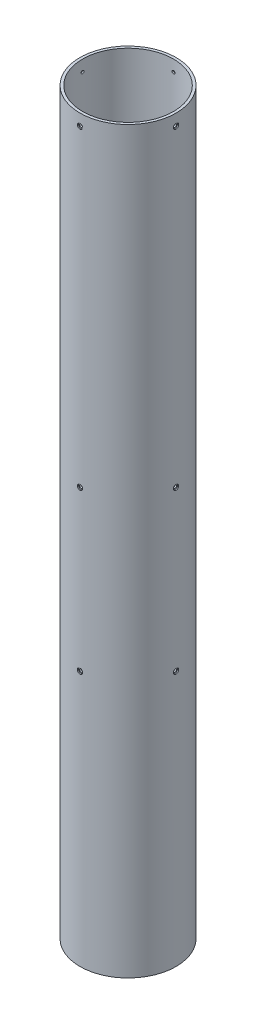
SolidWorks part; units mm, degrees
material "Hexcel AS4C (3000 Filaments)"
ref_plane "Front Plane" through (0, 0, 0) normal (0, 0, 1) x (1, 0, 0)
ref_plane "Top Plane" through (0, 0, 0) normal (0, 1, 0) x (1, 0, 0)
ref_plane "Right Plane" through (0, 0, 0) normal (1, 0, 0) x (0, 0, -1)
sketch "Sketch1" plane through (0, 0, 0) normal (0, 1, 0) x (1, 0, 0)
  circle A0 centre (0, 0) radius 50.8
  dimension "D1" = 101.6
extrude "Tube Extrusion" add sketch "Sketch1" along normal blind 825.5 thin thin type one direction wall 2.921
ref_plane "Hole Plane" through (0, 0, 53.721) normal (0, 0, 1) x (1, 0, 0)
sketch "Sketch3" plane through (0, 0, 53.721) normal (0, 0, 1) x (1, 0, 0)
  line L0 (0, 825.5) -> (0, 0) construction
  line L1 (50.8, 825.5) -> (-50.8, 825.5) construction
  line L2 (53.721, 825.5) -> (-53.721, 825.5) construction
  circle A0 centre (0, 463.55) radius 1.6383
  circle A1 centre (0, 285.75) radius 1.6383
  circle A2 centre (0, 812.8) radius 1.6383
  dimension "D1" = 3.2766
  dimension "D3" = 3.2766
  dimension "D5" = 3.2766
  dimension "D2" = 361.95
  dimension "D4" = 539.75
  dimension "D6" = 12.7
extrude "Bulkhead Holes" cut sketch "Sketch3" against normal up to next
pattern_circular "Hole Pattern" count 4 over 360 about axis through (0, 825.5, 0) along (0, -1, 0) of "Bulkhead Holes" reverse direction yes
sketch "Sketch4" plane through (0, 0, 53.721) normal (0, 0, 1) x (1, 0, 0)
  circle A0 centre (0, 285.75) radius 1.6383 construction
  circle A1 centre (0, 463.55) radius 1.6383 construction
  circle A2 centre (0, 812.8) radius 1.6383 construction
  circle A3 centre (0, 285.75) radius 1.6383
  circle A4 centre (0, 463.55) radius 1.6383
  circle A5 centre (0, 812.8) radius 1.6383
  circle A6 centre (0, 812.8) radius 2.9083
  circle A7 centre (0, 463.55) radius 2.9083
  circle A8 centre (0, 285.75) radius 2.9083
  dimension "D1" = 1.27
  dimension "D2" = 1.27
extrude "Cut-Extrude1" cut sketch "Sketch4" against normal blind 1.27
pattern_circular "CirPattern1" count 4 over 360 about axis through (0, 825.5, 0) along (0, -1, 0) of "Cut-Extrude1"
